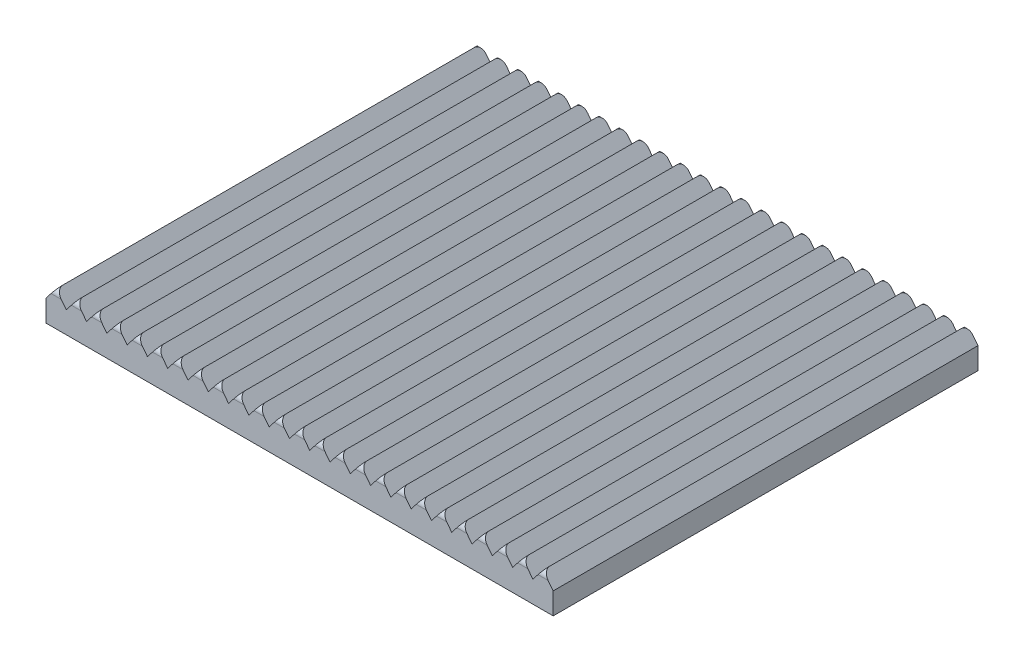
SolidWorks part; units mm, degrees
ref_plane "Front Plane" through (0, 0, 0) normal (0, 0, 1) x (1, 0, 0)
ref_plane "Top Plane" through (0, 0, 0) normal (0, 1, 0) x (1, 0, 0)
ref_plane "Right Plane" through (0, 0, 0) normal (1, 0, 0) x (0, 0, -1)
sketch "Sketch1" plane through (0, 0, 0) normal (0, 1, 0) x (1, 0, 0)
  line L6 (-29.25, 24.5) -> (29.25, 24.5)
  line L28 (-29.25, 24.5) -> (-29.25, -24.5)
  line L29 (-29.25, -24.5) -> (29.25, -24.5)
  line L30 (29.25, 24.5) -> (29.25, -24.5)
  line L31 (-29.25, 24.5) -> (29.25, -24.5) construction
  line L32 (-29.25, -24.5) -> (29.25, 24.5) construction
  circle A1 centre (0, 0) radius 3.1
  point P0 (0, 0)
  dimension "D3" = 6.2
  dimension "D1" = 58.5
  dimension "D2" = 49
extrude "Boss-Extrude1" add sketch "Sketch1" along normal blind 1.5
sketch "Sketch2" plane through (0, 0, -24.5) normal (0, 0, -1) x (-1, 0, 0)
  line L0 (-29.25, 1.5) -> (-29.25, 0) construction
  line L1 (-29.25, 1.5) -> (29.25, 1.5)
  line L2 (-29.25, 1.5) -> (-29.25, 2.5)
  line L4 (29.25, 1.5) -> (29.25, 2.5)
  line L5 (-1.17, 2.5) -> (0, 4)
  line L6 (0, 55) -> (0, -55) construction
  line L7 (1.17, 2.5) -> (0, 4)
  line L8 (1.17, 2.5) -> (2.34, 4)
  line L9 (3.51, 2.5) -> (2.34, 4)
  line L10 (3.51, 2.5) -> (4.68, 4)
  line L11 (5.85, 2.5) -> (4.68, 4)
  line L12 (5.85, 2.5) -> (7.02, 4)
  line L13 (8.19, 2.5) -> (7.02, 4)
  line L14 (8.19, 2.5) -> (9.36, 4)
  line L15 (10.53, 2.5) -> (9.36, 4)
  line L16 (10.53, 2.5) -> (11.7, 4)
  line L17 (12.87, 2.5) -> (11.7, 4)
  line L18 (12.87, 2.5) -> (14.04, 4)
  line L19 (15.21, 2.5) -> (14.04, 4)
  line L20 (15.21, 2.5) -> (16.38, 4)
  line L21 (17.55, 2.5) -> (16.38, 4)
  line L22 (17.55, 2.5) -> (18.72, 4)
  line L23 (19.89, 2.5) -> (18.72, 4)
  line L24 (19.89, 2.5) -> (21.06, 4)
  line L25 (22.23, 2.5) -> (21.06, 4)
  line L26 (22.23, 2.5) -> (23.4, 4)
  line L27 (24.57, 2.5) -> (23.4, 4)
  line L28 (24.57, 2.5) -> (25.74, 4)
  line L29 (26.91, 2.5) -> (25.74, 4)
  line L30 (26.91, 2.5) -> (28.08, 4)
  line L31 (29.25, 2.5) -> (28.08, 4)
  line L32 (-29.25, 2.5) -> (-28.08, 4)
  line L33 (-26.91, 2.5) -> (-28.08, 4)
  line L34 (-26.91, 2.5) -> (-25.74, 4)
  line L35 (-24.57, 2.5) -> (-25.74, 4)
  line L36 (-24.57, 2.5) -> (-23.4, 4)
  line L37 (-22.23, 2.5) -> (-23.4, 4)
  line L38 (-22.23, 2.5) -> (-21.06, 4)
  line L39 (-19.89, 2.5) -> (-21.06, 4)
  line L40 (-19.89, 2.5) -> (-18.72, 4)
  line L41 (-17.55, 2.5) -> (-18.72, 4)
  line L42 (-17.55, 2.5) -> (-16.38, 4)
  line L43 (-15.21, 2.5) -> (-16.38, 4)
  line L44 (-15.21, 2.5) -> (-14.04, 4)
  line L45 (-12.87, 2.5) -> (-14.04, 4)
  line L46 (-12.87, 2.5) -> (-11.7, 4)
  line L47 (-10.53, 2.5) -> (-11.7, 4)
  line L48 (-10.53, 2.5) -> (-9.36, 4)
  line L49 (-8.19, 2.5) -> (-9.36, 4)
  line L50 (-8.19, 2.5) -> (-7.02, 4)
  line L51 (-5.85, 2.5) -> (-7.02, 4)
  line L52 (-5.85, 2.5) -> (-4.68, 4)
  line L53 (-3.51, 2.5) -> (-4.68, 4)
  line L54 (-3.51, 2.5) -> (-2.34, 4)
  line L55 (-1.17, 2.5) -> (-2.34, 4)
  dimension "D1" = 1
  dimension "D2" = 1.5
  dimension "D3" = 13
extrude "Boss-Extrude2" add sketch "Sketch2" against normal blind 49
sketch "Sketch3" plane through (0, 0, 0) normal (0, -1, 0) x (-1, 0, 0)
  line L0 (0, 0.825) -> (0, -0.825) construction
  line L2 (-1.75, -2.5588) -> (-1.75, -5)
  line L3 (-1.75, -5) -> (1.75, -5)
  line L4 (1.75, -2.5588) -> (1.75, -5)
  arc A0 (1.75, -2.5588) -> (-1.75, -2.5588) centre (0, 0) ccw
  dimension "D2" = 6.2
  dimension "D1" = 3.5
  dimension "D3" = 5
  dimension "D4" = 1.75
extrude "Cut-Extrude1" cut sketch "Sketch3" against normal blind 2
chamfer "Chamfer2" distance 0.2 angle 45 1 edges at (0, 0, -3.1)
sketch "Sketch4" plane through (29.25, 0, 0) normal (1, 0, 0) x (0, 0, -1)
  line L1 (-24.5, 4) -> (-24.5, 2.5) construction
  line L2 (-24.5, 4) -> (24.5, 4) construction
  line L3 (-23.75, 4) -> (-24.5, 4)
  line L4 (-24.5, 4) -> (-24.5, 3.25)
  arc A0 (-24.5, 3.25) -> (-23.75, 4) centre (-23.75, 3.25) cw
extrude "Cut-Extrude3" cut sketch "Sketch4" against normal through all
mirror "Mirror1" about plane through (0, 0, 0) normal (0, 0, 1) of "Cut-Extrude3"
chamfer "Chamfer3" distance 2 angle 45 1 edges at (0, 0, 5)
